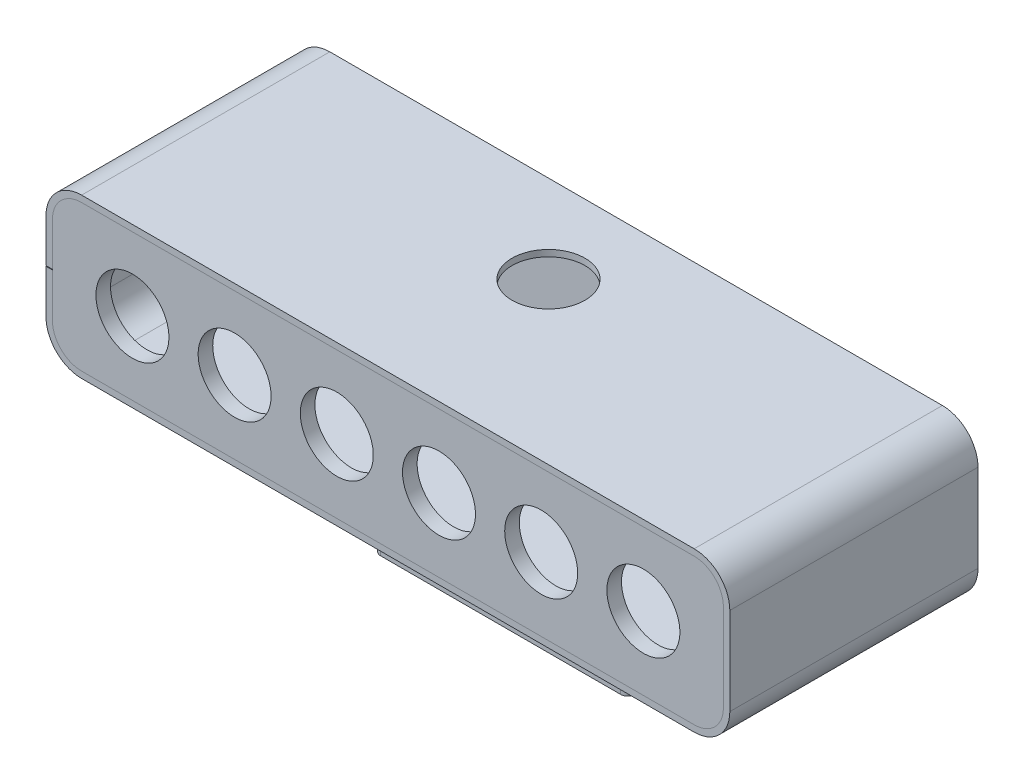
SolidWorks part; units mm, degrees
material "Acrylic (Medium-high impact)"
ref_plane "Front" through (0, 0, 0) normal (0, 0, 1) x (1, 0, 0)
ref_plane "Top" through (0, 0, 0) normal (0, 1, 0) x (1, 0, 0)
ref_plane "Right" through (0, 0, 0) normal (1, 0, 0) x (0, 0, -1)
sketch "Sketch5" plane through (0, 0, 0) normal (0, 1, 0) x (1, 0, 0)
  line L1 (0, 0) -> (-698.5, 0)
  line L2 (0, 0) -> (0, 101.6)
  line L3 (0, 101.6) -> (-698.5, 101.6)
  line L4 (-698.5, 0) -> (-698.5, 101.6)
  dimension "D1" = 101.6
  dimension "D2" = 698.5
extrude "Boss-Extrude4" [suppressed] add sketch "Sketch5" along normal blind 2.794
sketch "Sketch1" plane through (0, 0, 0) normal (0, 0, 1) x (1, 0, 0)
  line L1 (-145.923, 31.75) -> (145.923, 31.75)
  line L2 (-145.923, 31.75) -> (-145.923, -31.75)
  line L3 (-145.923, -31.75) -> (145.923, -31.75)
  line L4 (145.923, 31.75) -> (145.923, -31.75)
  line L5 (-145.923, 31.75) -> (145.923, -31.75) construction
  line L6 (-145.923, -31.75) -> (145.923, 31.75) construction
  point P0 (0, 0)
  dimension "D1" = 291.846
  dimension "D2" = 63.5
extrude "Boss-Extrude1" add sketch "Sketch1" along normal blind 6.35
fillet "Fillet1" radius 12.7 4 edges at (-145.923, -31.75, 3.175) (145.923, -31.75, 3.175) (145.923, 31.75, 3.175) (-145.923, 31.75, 3.175)
sketch "Sketch3" plane through (0, 0, 0) normal (0, 0, 1) x (1, 0, 0)
  line L0 (133.223, 34.544) -> (-133.223, 34.544)
  line L1 (-148.717, 19.05) -> (-148.717, 0.254)
  line L2 (-133.223, -34.544) -> (133.223, -34.544)
  line L3 (148.717, -19.05) -> (148.717, 19.05)
  line L4 (-133.223, -31.75) -> (133.223, -31.75)
  line L5 (-145.923, 19.05) -> (-145.923, -19.05)
  line L6 (133.223, 31.75) -> (-133.223, 31.75)
  line L7 (145.923, -19.05) -> (145.923, 19.05)
  line L8 (-133.223, -31.75) -> (133.223, -31.75)
  line L9 (-145.923, 19.05) -> (-145.923, 0.254)
  line L10 (133.223, 31.75) -> (-133.223, 31.75)
  line L11 (145.923, -19.05) -> (145.923, 19.05)
  line L12 (-145.923, 0) -> (-148.717, 0)
  line L13 (-145.923, 0.254) -> (-148.717, 0.254)
  line L14 (-145.923, 0) -> (-145.923, -19.05)
  line L15 (-145.923, 19.05) -> (-145.923, -19.05) construction
  line L16 (-148.717, 0) -> (-148.717, -19.05)
  line L17 (-148.717, 19.05) -> (-148.717, -19.05) construction
  line L18 (-145.923, 19.05) -> (-145.923, -19.05) construction
  arc A0 (-133.223, 34.544) -> (-148.717, 19.05) centre (-133.223, 19.05) ccw
  arc A1 (-148.717, -19.05) -> (-133.223, -34.544) centre (-133.223, -19.05) ccw
  arc A2 (133.223, -34.544) -> (148.717, -19.05) centre (133.223, -19.05) ccw
  arc A3 (148.717, 19.05) -> (133.223, 34.544) centre (133.223, 19.05) ccw
  arc A4 (-145.923, -19.05) -> (-133.223, -31.75) centre (-133.223, -19.05) ccw
  arc A5 (-133.223, 31.75) -> (-145.923, 19.05) centre (-133.223, 19.05) ccw
  arc A6 (145.923, 19.05) -> (133.223, 31.75) centre (133.223, 19.05) ccw
  arc A7 (133.223, -31.75) -> (145.923, -19.05) centre (133.223, -19.05) ccw
  arc A8 (-145.923, -19.05) -> (-133.223, -31.75) centre (-133.223, -19.05) ccw
  arc A9 (-133.223, 31.75) -> (-145.923, 19.05) centre (-133.223, 19.05) ccw
  arc A10 (145.923, 19.05) -> (133.223, 31.75) centre (133.223, 19.05) ccw
  arc A11 (133.223, -31.75) -> (145.923, -19.05) centre (133.223, -19.05) ccw
  dimension "D3" = 0.254
  dimension "D1" = 0
  dimension "D2" = 2.794
extrude "Boss-Extrude2" add sketch "Sketch3" along normal blind 107.95 separate body
sketch "Sketch4" plane through (0, 0, 107.95) normal (0, 0, 1) x (1, 0, 0)
  line L4 (-145.923, 19.05) -> (-145.923, -19.05)
  line L5 (-133.223, -31.75) -> (133.223, -31.75)
  line L6 (145.923, -19.05) -> (145.923, 19.05)
  line L7 (133.223, 31.75) -> (-133.223, 31.75)
  line L8 (-145.923, 19.05) -> (-145.923, -19.05)
  line L9 (-133.223, -31.75) -> (133.223, -31.75)
  line L10 (145.923, -19.05) -> (145.923, 19.05)
  line L11 (133.223, 31.75) -> (-133.223, 31.75)
  arc A4 (-145.923, -19.05) -> (-133.223, -31.75) centre (-133.223, -19.05) ccw
  arc A5 (133.223, -31.75) -> (145.923, -19.05) centre (133.223, -19.05) ccw
  arc A6 (145.923, 19.05) -> (133.223, 31.75) centre (133.223, 19.05) ccw
  arc A7 (-133.223, 31.75) -> (-145.923, 19.05) centre (-133.223, 19.05) ccw
  arc A8 (-145.923, -19.05) -> (-133.223, -31.75) centre (-133.223, -19.05) ccw
  arc A9 (133.223, -31.75) -> (145.923, -19.05) centre (133.223, -19.05) ccw
  arc A10 (145.923, 19.05) -> (133.223, 31.75) centre (133.223, 19.05) ccw
  arc A11 (-133.223, 31.75) -> (-145.923, 19.05) centre (-133.223, 19.05) ccw
  dimension "D1" = 0
extrude "Boss-Extrude3" add sketch "Sketch4" against normal blind 6.35 separate body
sketch "Sketch2" plane through (0, 0, 0) normal (0, 0, -1) x (-1, 0, 0)
  line L0 (22.225, 0) -> (-22.225, 0) construction
  line L1 (22.225, 0) -> (66.675, 0) construction
  line L2 (66.675, 0) -> (111.125, 0) construction
  line L3 (-22.225, 0) -> (-66.675, 0) construction
  line L4 (-66.675, 0) -> (-111.125, 0) construction
  line L5 (-111.125, 0) -> (-127, 0) construction
  line L6 (111.125, 0) -> (127, 0) construction
  circle A0 centre (-111.125, 0) radius 15.875
  circle A1 centre (-66.675, 0) radius 15.875
  circle A2 centre (-22.225, 0) radius 15.875
  circle A3 centre (22.225, 0) radius 15.875
  circle A4 centre (66.675, 0) radius 15.875
  circle A5 centre (111.125, 0) radius 15.875
  dimension "D1" = 31.75
  dimension "D2" = 254
extrude "Cut-Extrude1" cut sketch "Sketch2" against normal through all
sketch "Sketch6" plane through (0, -34.544, 0) normal (0, -1, 0) x (1, 0, 0)
  line L0 (0, 0) -> (0, 31.369) construction
  line L1 (-133.223, 0) -> (133.223, 0) construction
  line L2 (-52.705, 55.928) -> (-52.705, 6.81)
  line L3 (-52.245, 58.928) -> (52.245, 58.928)
  line L4 (-55.245, 55.928) -> (-55.245, 6.81)
  line L5 (-52.245, 3.81) -> (52.245, 3.81)
  line L6 (55.245, 55.928) -> (55.245, 6.81)
  line L7 (-55.245, 58.928) -> (55.245, 3.81) construction
  line L8 (-55.245, 3.81) -> (55.245, 58.928) construction
  line L9 (-52.245, 6.35) -> (52.245, 6.35)
  line L10 (52.705, 55.928) -> (52.705, 6.81)
  line L11 (-52.245, 56.388) -> (52.245, 56.388)
  arc A0 (-55.245, 6.81) -> (-52.245, 3.81) centre (-52.245, 6.81) ccw
  arc A1 (55.245, 6.81) -> (52.245, 3.81) centre (52.245, 6.81) cw
  arc A2 (55.245, 55.928) -> (52.245, 58.928) centre (52.245, 55.928) ccw
  arc A3 (-52.245, 58.928) -> (-55.245, 55.928) centre (-52.245, 55.928) ccw
  arc A4 (-52.705, 6.81) -> (-52.245, 6.35) centre (-52.245, 6.81) ccw
  arc A5 (52.705, 6.81) -> (52.245, 6.35) centre (52.245, 6.81) cw
  arc A6 (52.705, 55.928) -> (52.245, 56.388) centre (52.245, 55.928) ccw
  arc A7 (-52.245, 56.388) -> (-52.705, 55.928) centre (-52.245, 55.928) ccw
  dimension "D4" = 3
  dimension "D1" = 110.49
  dimension "D2" = 55.118
  dimension "D3" = 3.81
  dimension "D5" = 2.54
extrude "Boss-Extrude5" add sketch "Sketch6" along normal blind 50.8 separate body
sketch "Sketch7" plane through (0, 0, 0) normal (0, 0, -1) x (-1, 0, 0)
  line L0 (0, 0) -> (-52.3875, 0) construction
  line L1 (0, 0) -> (52.3875, 0) construction
  circle A0 centre (-52.3875, 0) radius 3.175
  circle A1 centre (52.3875, 0) radius 3.175
  dimension "D1" = 6.35
  dimension "D2" = 104.775
extrude "Cut-Extrude2" cut sketch "Sketch7" against normal up to next (6.35 mm away)
sketch "Sketch8" plane through (0, -34.544, 0) normal (0, -1, 0) x (1, 0, 0)
  line L0 (0, 3.81) -> (0, 58.928) construction
  line L1 (-52.245, 3.81) -> (52.245, 3.81) construction
  line L2 (52.245, 58.928) -> (-52.245, 58.928) construction
  line L4 (-46.355, 53.594) -> (46.355, 53.594)
  line L5 (-50.165, 49.784) -> (-50.165, 12.954)
  line L6 (-46.355, 9.144) -> (46.355, 9.144)
  line L7 (50.165, 49.784) -> (50.165, 12.954)
  line L8 (-50.165, 53.594) -> (50.165, 9.144) construction
  line L9 (-50.165, 9.144) -> (50.165, 53.594) construction
  arc A0 (-50.165, 12.954) -> (-46.355, 9.144) centre (-46.355, 12.954) ccw
  arc A1 (50.165, 12.954) -> (46.355, 9.144) centre (46.355, 12.954) cw
  arc A2 (50.165, 49.784) -> (46.355, 53.594) centre (46.355, 49.784) ccw
  arc A3 (-46.355, 53.594) -> (-50.165, 49.784) centre (-46.355, 49.784) ccw
  point P6 (0, 31.369)
  dimension "D3" = 3.81
  dimension "D1" = 100.33
  dimension "D2" = 44.45
extrude "Cut-Extrude3" cut sketch "Sketch8" against normal up to next (2.794 mm away)
sketch "Sketch9" plane through (0, -34.544, 0) normal (0, -1, 0) x (1, 0, 0)
  line L2 (0, 0) -> (0, 38.1) construction
  circle A0 centre (0, 38.1) radius 15.875
  point P2 (1.3801, 30.4825)
  dimension "D1" = 31.75
  dimension "D2" = 38.1
extrude "Cut-Extrude4" cut sketch "Sketch9" against normal through all from surface starting at face at (0, 31.75, 53.975)
